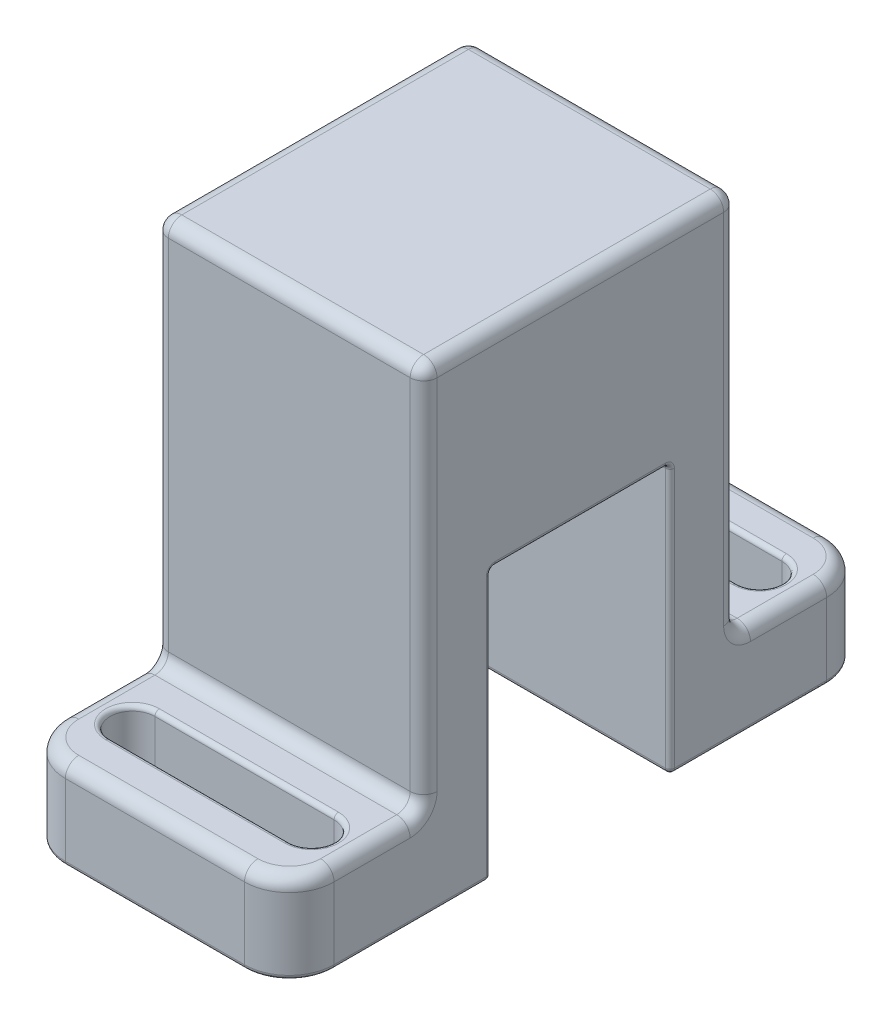
SolidWorks part; units mm, degrees
ref_plane "Front Plane" through (0, 0, 0) normal (0, 0, 1) x (1, 0, 0)
ref_plane "Top Plane" through (0, 0, 0) normal (0, 1, 0) x (1, 0, 0)
ref_plane "Right Plane" through (0, 0, 0) normal (1, 0, 0) x (0, 0, -1)
sketch "Sketch1" plane through (0, 0, 0) normal (0, 1, 0) x (1, 0, 0)
  line L1 (-15, 17.5) -> (15, 17.5)
  line L2 (-15, 17.5) -> (-15, -17.5)
  line L3 (-15, -17.5) -> (15, -17.5)
  line L4 (15, 17.5) -> (15, -17.5)
  line L5 (-15, 17.5) -> (15, -17.5) construction
  line L6 (-15, -17.5) -> (15, 17.5) construction
  point P0 (0, 0)
  dimension "D1" = 35
  dimension "D2" = 30
extrude "Boss-Extrude1" add sketch "Sketch1" along normal blind 53
sketch "Sketch2" plane through (0, 0, 0) normal (0, -1, 0) x (1, 0, 0)
  line L0 (15, 17.5) -> (15, -17.5) construction
  line L1 (-15, 32.5) -> (15, 32.5)
  line L2 (-15, 32.5) -> (-15, -32.5)
  line L3 (-15, -32.5) -> (15, -32.5)
  line L4 (15, 32.5) -> (15, -32.5)
  line L5 (-15, 32.5) -> (15, -32.5) construction
  line L6 (-15, -32.5) -> (15, 32.5) construction
  line L7 (-10, 25) -> (10, 25) construction
  line L8 (-10, 27.5) -> (10, 27.5)
  line L9 (-10, 22.5) -> (10, 22.5)
  line L10 (16.5, 0) -> (-16.5, 0) construction
  line L11 (-10, -25) -> (10, -25) construction
  line L12 (-10, -27.5) -> (10, -27.5)
  line L13 (-10, -22.5) -> (10, -22.5)
  arc A0 (-10, 27.5) -> (-10, 22.5) centre (-10, 25) ccw
  arc A1 (10, 22.5) -> (10, 27.5) centre (10, 25) ccw
  arc A2 (-10, -27.5) -> (-10, -22.5) centre (-10, -25) cw
  arc A3 (10, -22.5) -> (10, -27.5) centre (10, -25) cw
  point P0 (0, 0)
  point P10 (0, 25)
  point P22 (0, -25)
  dimension "D2" = 2.5
  dimension "D1" = 65
  dimension "D4" = 5
extrude "Boss-Extrude2" add sketch "Sketch2" against normal blind 10
sketch "Sketch3" plane through (-15, 0, 0) normal (-1, 0, 0) x (0, 0, 1)
  line L0 (-32.5, 0) -> (32.5, 0) construction
  line L1 (-10, 30) -> (10, 30)
  line L2 (-10, 30) -> (-10, 0)
  line L3 (-10, 0) -> (10, 0)
  line L4 (10, 30) -> (10, 0)
  line L5 (-10, 30) -> (10, 0) construction
  line L6 (-10, 0) -> (10, 30) construction
  point P0 (0, 15)
  dimension "D1" = 20
  dimension "D2" = 30
extrude "Cut-Extrude1" cut sketch "Sketch3" against normal through all both and the other way through all
fillet "Fillet1" radius 1.5 16 edges at (15, 10, -25) (-15, 10, -25) (-15, 10, 25) (15, 10, 25) (-15, 53, 0) (15, 53, 0) (15, 31.5, -17.5) (0, 53, -17.5) (-15, 31.5, -17.5) (0, 10, -17.5) (-15, 31.5, 17.5) (0, 53, 17.5) (15, 31.5, 17.5) (0, 10, 17.5) (0, 10, -32.5) (0, 10, 32.5)
fillet "Fillet2" radius 5 8 edges at (14.5607, 9.5607, -32.0607) (-14.5607, 9.5607, -32.0607) (-14.5607, 9.5607, 32.0607) (14.5607, 9.5607, 32.0607) (15, 4.25, 32.5) (-15, 4.25, 32.5) (-15, 4.25, -32.5) (15, 4.25, -32.5)
fillet "Fillet3" radius 0.5 36 edges at (-15, 15, 10) (-15, 30, 0) (15, 15, -10) (-15, 0, 18.75) (-13.5355, 0, 31.0355) (0, 0, 32.5) (13.5355, 0, 31.0355) (-15, 0, -18.75) (-13.5355, 0, -31.0355) (0, 0, -32.5) (13.5355, 0, -31.0355) (12.5, 0, -25) (0, 0, -27.5) (-12.5, 0, -25) (12.5, 0, 25) (0, 0, 22.5) (-12.5, 0, 25) (12.5, 10, -25) (0, 10, -27.5) (-12.5, 10, -25) (12.5, 10, 25) (0, 10, 22.5) (-12.5, 10, 25) (-15, 15, -10) (0, 0, -10) (0, 30, -10) (0, 30, 10) (15, 30, 0) (15, 15, 10) (0, 0, 10) (15, 0, 18.75) (15, 0, -18.75) (0, 0, -22.5) (0, 0, 27.5) (0, 10, -22.5) (0, 10, 27.5)
